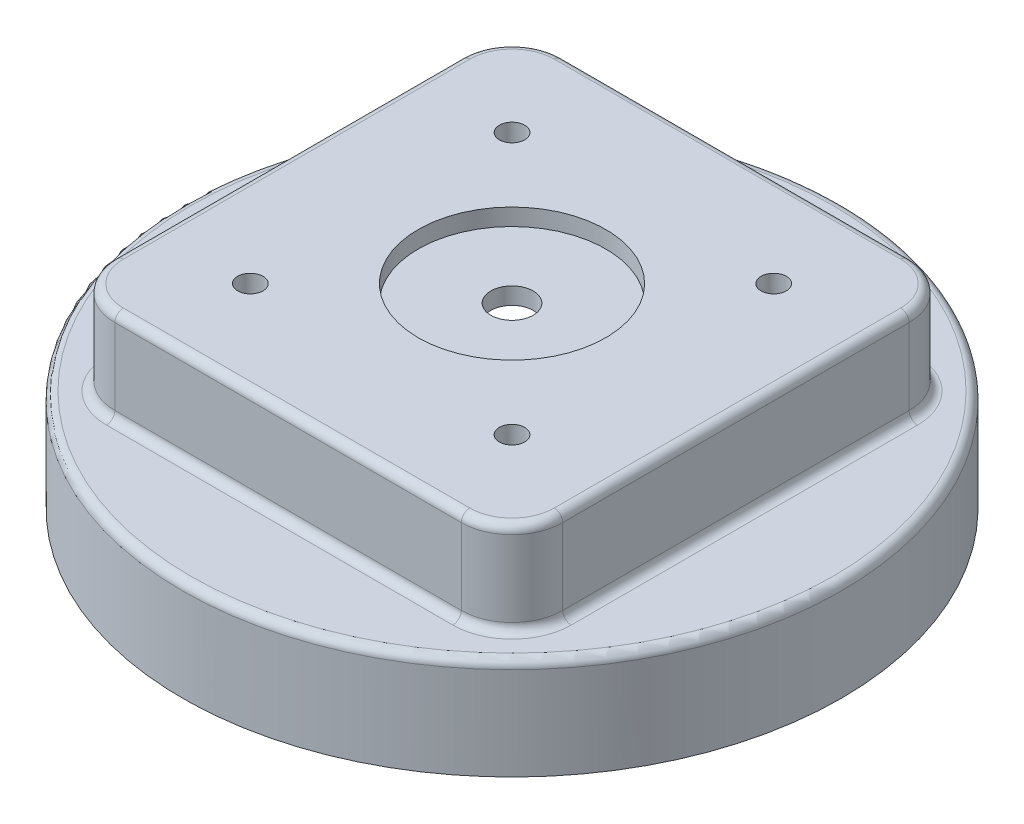
SolidWorks part; units mm, degrees
material "Acrylic (Medium-high impact)"
ref_plane "Front Plane" through (0, 0, 0) normal (0, 0, 1) x (1, 0, 0)
ref_plane "Top Plane" through (0, 0, 0) normal (0, 1, 0) x (1, 0, 0)
ref_plane "Right Plane" through (0, 0, 0) normal (1, 0, 0) x (0, 0, -1)
sketch "Sketch1" plane through (0, 0, 0) normal (0, 1, 0) x (1, 0, 0)
  circle A0 centre (0, 0) radius 35
  circle A1 centre (0, 0) radius 39
extrude "Boss-Extrude1" add sketch "Sketch1" along normal blind 8
sketch "Sketch2" plane through (0, 8, 0) normal (0, 1, 0) x (1, 0, 0)
  line L1 (-20.5, -22.5) -> (20.5, -22.5)
  line L2 (-22.5, -20.5) -> (-22.5, 20.5)
  line L3 (-20.5, 22.5) -> (20.5, 22.5)
  line L4 (22.5, -20.5) -> (22.5, 20.5)
  line L5 (-22.5, -22.5) -> (22.5, 22.5) construction
  line L6 (-22.5, 22.5) -> (22.5, -22.5) construction
  circle A0 centre (0, 0) radius 39
  arc A1 (-20.5, -22.5) -> (-22.5, -20.5) centre (-20.5, -20.5) cw
  arc A2 (20.5, -22.5) -> (22.5, -20.5) centre (20.5, -20.5) ccw
  arc A3 (20.5, 22.5) -> (22.5, 20.5) centre (20.5, 20.5) cw
  arc A4 (-22.5, 20.5) -> (-20.5, 22.5) centre (-20.5, 20.5) cw
  dimension "D3" = 2
  dimension "D1" = 45
  dimension "D2" = 45
extrude "Boss-Extrude2" add sketch "Sketch2" along normal blind 4
sketch "Sketch3" plane through (0, 12, 0) normal (0, 1, 0) x (1, 0, 0)
  line L5 (-20.5, -22.5) -> (20.5, -22.5)
  line L6 (22.5, -20.5) -> (22.5, 20.5)
  line L7 (20.5, 22.5) -> (-20.5, 22.5)
  line L8 (-22.5, 20.5) -> (-22.5, -20.5)
  line L9 (-20.5, -26.5) -> (20.5, -26.5)
  line L10 (26.5, -20.5) -> (26.5, 20.5)
  line L11 (20.5, 26.5) -> (-20.5, 26.5)
  line L12 (-26.5, 20.5) -> (-26.5, -20.5)
  line L13 (-20.5, -26.5) -> (20.5, -26.5)
  line L14 (26.5, -20.5) -> (26.5, 20.5)
  line L15 (20.5, 26.5) -> (-20.5, 26.5)
  line L16 (-26.5, 20.5) -> (-26.5, -20.5)
  arc A6 (20.5, -22.5) -> (22.5, -20.5) centre (20.5, -20.5) ccw
  arc A7 (22.5, 20.5) -> (20.5, 22.5) centre (20.5, 20.5) ccw
  arc A8 (-20.5, 22.5) -> (-22.5, 20.5) centre (-20.5, 20.5) ccw
  arc A9 (-22.5, -20.5) -> (-20.5, -22.5) centre (-20.5, -20.5) ccw
  arc A10 (-26.5, -20.5) -> (-20.5, -26.5) centre (-20.5, -20.5) ccw
  arc A11 (20.5, -26.5) -> (26.5, -20.5) centre (20.5, -20.5) ccw
  arc A12 (26.5, 20.5) -> (20.5, 26.5) centre (20.5, 20.5) ccw
  arc A13 (-20.5, 26.5) -> (-26.5, 20.5) centre (-20.5, 20.5) ccw
  arc A14 (-26.5, -20.5) -> (-20.5, -26.5) centre (-20.5, -20.5) ccw
  arc A15 (20.5, -26.5) -> (26.5, -20.5) centre (20.5, -20.5) ccw
  arc A16 (26.5, 20.5) -> (20.5, 26.5) centre (20.5, 20.5) ccw
  arc A17 (-20.5, 26.5) -> (-26.5, 20.5) centre (-20.5, 20.5) ccw
  dimension "D1" = 4
  dimension "D2" = 4
extrude "Boss-Extrude3" add sketch "Sketch3" along normal blind 7
sketch "Sketch4" plane through (0, 19, 0) normal (0, 1, 0) x (1, 0, 0)
  line L8 (-20.5, -26.5) -> (20.5, -26.5)
  line L9 (26.5, -20.5) -> (26.5, 20.5)
  line L10 (20.5, 26.5) -> (-20.5, 26.5)
  line L11 (-26.5, 20.5) -> (-26.5, -20.5)
  line L12 (-20.5, -26.5) -> (20.5, -26.5)
  line L13 (26.5, -20.5) -> (26.5, 20.5)
  line L14 (20.5, 26.5) -> (-20.5, 26.5)
  line L15 (-26.5, 20.5) -> (-26.5, -20.5)
  arc A8 (-26.5, -20.5) -> (-20.5, -26.5) centre (-20.5, -20.5) ccw
  arc A9 (20.5, -26.5) -> (26.5, -20.5) centre (20.5, -20.5) ccw
  arc A10 (26.5, 20.5) -> (20.5, 26.5) centre (20.5, 20.5) ccw
  arc A11 (-20.5, 26.5) -> (-26.5, 20.5) centre (-20.5, 20.5) ccw
  arc A12 (-26.5, -20.5) -> (-20.5, -26.5) centre (-20.5, -20.5) ccw
  arc A13 (20.5, -26.5) -> (26.5, -20.5) centre (20.5, -20.5) ccw
  arc A14 (26.5, 20.5) -> (20.5, 26.5) centre (20.5, 20.5) ccw
  arc A15 (-20.5, 26.5) -> (-26.5, 20.5) centre (-20.5, 20.5) ccw
  dimension "D1" = 0
extrude "Boss-Extrude4" add sketch "Sketch4" along normal blind 4
sketch "Sketch5" plane through (0, 23, 0) normal (0, 1, 0) x (1, 0, 0)
  circle A0 centre (0, 0) radius 11.1
extrude "Cut-Extrude1" cut sketch "Sketch5" against normal blind 2
sketch "Sketch6" plane through (0, 23, 0) normal (0, 1, 0) x (1, 0, 0)
  line L0 (-24.7426, 24.7426) -> (24.7426, -24.7426) construction
  line L1 (-24.7426, -24.7426) -> (24.7426, 24.7426) construction
  arc A0 (-20.5, 26.5) -> (-26.5, 20.5) centre (-20.5, 20.5) ccw construction
  arc A1 (20.5, -26.5) -> (26.5, -20.5) centre (20.5, -20.5) ccw construction
  arc A2 (-26.5, -20.5) -> (-20.5, -26.5) centre (-20.5, -20.5) ccw construction
  arc A3 (26.5, 20.5) -> (20.5, 26.5) centre (20.5, 20.5) ccw construction
  circle A4 centre (0, 0) radius 21.9 construction
  circle A5 centre (-15.4856, 15.4856) radius 1.5
  circle A6 centre (15.4856, 15.4856) radius 1.5
  circle A7 centre (15.4856, -15.4856) radius 1.5
  circle A8 centre (-15.4856, -15.4856) radius 1.5
  circle A9 centre (0, 0) radius 2.5
  point P29 (0, 0)
  dimension "D1" = 4
extrude "Cut-Extrude2" cut sketch "Sketch6" against normal through all
fillet "Fillet1" radius 1 9 edges at (24.7426, 12, 24.7426) (26.5, 12, 0) (24.7426, 12, -24.7426) (0, 12, -26.5) (-24.7426, 12, -24.7426) (-26.5, 12, 0) (-24.7426, 12, 24.7426) (0, 12, 26.5) (0, 12, 39)
fillet "Fillet2" radius 1 8 edges at (-24.7426, 23, -24.7426) (0, 23, -26.5) (24.7426, 23, -24.7426) (26.5, 23, 0) (24.7426, 23, 24.7426) (0, 23, 26.5) (-24.7426, 23, 24.7426) (-26.5, 23, 0)
sketch "Sketch7" plane through (0, 0, 0) normal (1, 0, 0) x (0, 0, -1)
  line L0 (-20.5, 8) -> (20.5, 8) construction
  circle A0 centre (0, -2.75) radius 10.6
  dimension "D1" = 21.2
  dimension "D2" = 10.75
extrude "Cut-Extrude3" cut sketch "Sketch7" against normal blind 50
